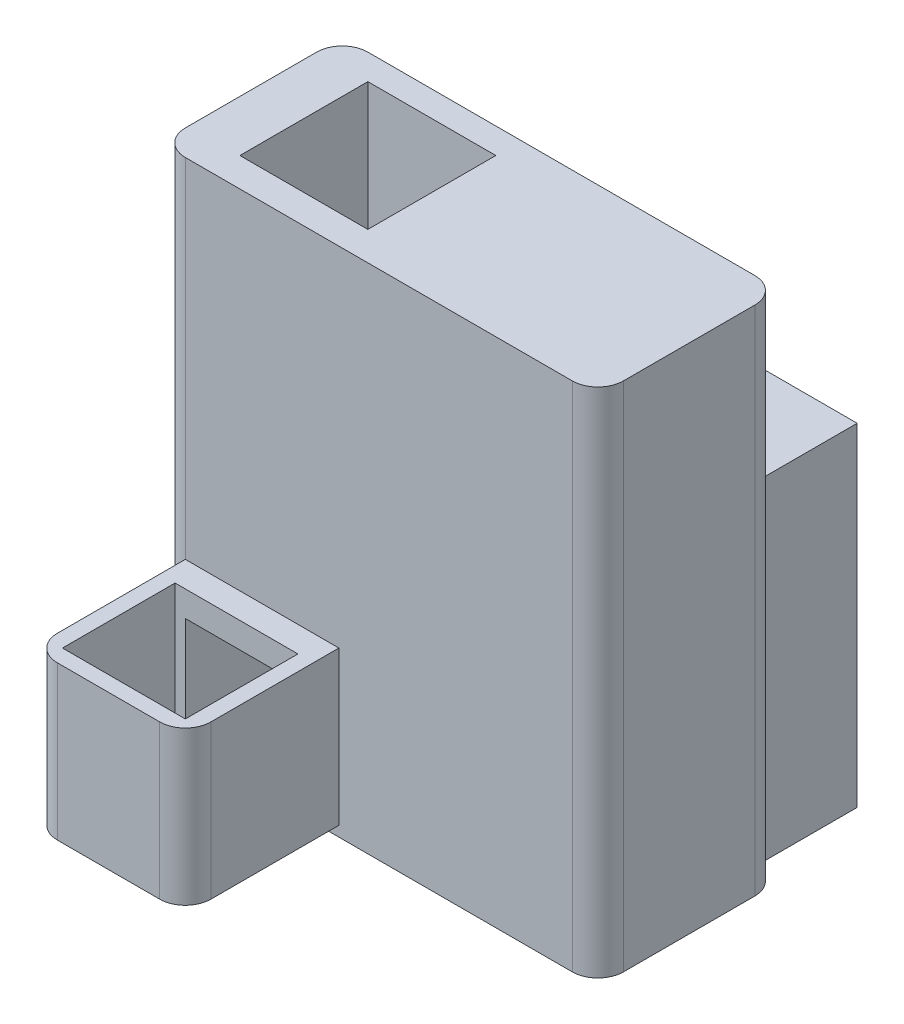
SolidWorks part; units mm, degrees
ref_plane "Alzado" through (0, 0, 0) normal (0, 0, 1) x (1, 0, 0)
ref_plane "Planta" through (0, 0, 0) normal (0, 1, 0) x (1, 0, 0)
ref_plane "Vista lateral" through (0, 0, 0) normal (1, 0, 0) x (0, 0, -1)
sketch "Croquis1" plane through (0, 0, 0) normal (0, 1, 0) x (1, 0, 0)
  line L1 (-42.8, 17.83) -> (42.8, 17.83)
  line L2 (-42.8, 17.83) -> (-42.8, -17.83)
  line L3 (-42.8, -17.83) -> (42.8, -17.83)
  line L4 (42.8, 17.83) -> (42.8, -17.83)
  line L5 (-42.8, 17.83) -> (42.8, -17.83) construction
  line L6 (-42.8, -17.83) -> (42.8, 17.83) construction
  point P0 (0, 0)
  dimension "D1" = 85.6
  dimension "D2" = 35.66
extrude "Saliente-Extruir1" add sketch "Croquis1" along normal blind 100
sketch "Croquis2" plane through (0, 100, 0) normal (0, 1, 0) x (1, 0, 0)
  line L0 (42.8, 17.83) -> (-42.8, 17.83) construction
  line L1 (-32.8, 12.83) -> (-7.8, 12.83)
  line L2 (-32.8, 12.83) -> (-32.8, -12.17)
  line L3 (-32.8, -12.17) -> (-7.8, -12.17)
  line L4 (-7.8, 12.83) -> (-7.8, -12.17)
  line L5 (-32.8, 12.83) -> (-7.8, -12.17) construction
  line L6 (-32.8, -12.17) -> (-7.8, 12.83) construction
  line L7 (-42.8, 17.83) -> (-42.8, -17.83) construction
  point P0 (-20.3, 0.33)
  dimension "D1" = 5
  dimension "D2" = 10
  dimension "D3" = 25
  dimension "D4" = 25
extrude "Cortar-Extruir1" cut sketch "Croquis2" against normal blind 92
sketch "Croquis3" plane through (0, 0, 17.83) normal (0, 0, 1) x (1, 0, 0)
  line L0 (-42.8, 100) -> (-42.8, 0) construction
  line L1 (-37.8, 32) -> (-7.8, 32)
  line L2 (-37.8, 32) -> (-37.8, 2)
  line L3 (-37.8, 2) -> (-7.8, 2)
  line L4 (-7.8, 32) -> (-7.8, 2)
  line L5 (-37.8, 32) -> (-7.8, 2) construction
  line L6 (-37.8, 2) -> (-7.8, 32) construction
  line L9 (-42.8, 0) -> (42.8, 0) construction
  point P0 (-22.8, 17)
  dimension "D1" = 5
  dimension "D2" = 2
  dimension "D3" = 30
  dimension "D4" = 30
extrude "Saliente-Extruir2" add sketch "Croquis3" along normal blind 30
sketch "Croquis4" plane through (0, 2, 0) normal (0, -1, 0) x (1, 0, 0)
  line L0 (-7.8, 47.83) -> (-7.8, 17.83) construction
  line L1 (-37.8, 47.83) -> (-37.8, 17.83) construction
  line L2 (-37.8, 47.83) -> (-7.8, 47.83) construction
  line L20 (-34.8, 22.83) -> (-10.8, 22.83)
  line L21 (-10.8, 22.83) -> (-10.8, 44.83)
  line L22 (-10.8, 44.83) -> (-34.8, 44.83)
  line L23 (-34.8, 44.83) -> (-34.8, 22.83)
  dimension "D1" = 3
  dimension "D2" = 3
  dimension "D3" = 3
extrude "Cortar-Extruir2" cut sketch "Croquis4" against normal up to surface (30 mm away) up to face at (-22.8, 32, 32.83)
sketch "Croquis6" plane through (0, 0, 17.83) normal (0, 0, 1) x (1, 0, 0)
  line L8 (-12.8, 7) -> (-12.8, 27)
  line L9 (-12.8, 27) -> (-32.8, 27)
  line L10 (-32.8, 27) -> (-32.8, 7)
  line L11 (-32.8, 7) -> (-12.8, 7)
  line L12 (-12.8, 7) -> (-12.8, 27)
  line L13 (-12.8, 27) -> (-32.8, 27)
  line L14 (-32.8, 27) -> (-32.8, 7)
  line L15 (-32.8, 7) -> (-12.8, 7)
  dimension "D1" = 5
fillet "Redondeo1" radius 5 6 edges at (42.8, 50, 17.83) (42.8, 50, -17.83) (-42.8, 50, -17.83) (-42.8, 50, 17.83) (-7.8, 17, 47.83) (-37.8, 17, 47.83)
sketch "Croquis8" plane through (0, 0, -17.83) normal (0, 0, -1) x (-1, 0, 0)
  line L0 (37.8, 0) -> (37.8, 100) construction
  line L1 (-37.8, 0) -> (37.8, 0)
  line L2 (-37.8, 0) -> (-37.8, 65)
  line L3 (-37.8, 65) -> (37.8, 65)
  line L4 (37.8, 0) -> (37.8, 65)
  dimension "D1" = 75.6
  dimension "D2" = 65
extrude "Saliente-Extruir3" add sketch "Croquis8" along normal blind 20
extrude "Cortar-Extruir3" cut sketch "Croquis6" against normal blind 10 and the other way blind 10
sketch "Croquis9" plane through (0, 2, 0) normal (0, -1, 0) x (1, 0, 0)
  line L0 (-10.8, 22.83) -> (-10.8, 44.83) construction
  line L1 (-34.8, 22.83) -> (-10.8, 22.83)
  line L2 (-34.8, 22.83) -> (-34.8, 44.83)
  line L3 (-34.8, 44.83) -> (-10.8, 44.83)
  line L4 (-10.8, 22.83) -> (-10.8, 44.83)
  line L5 (-10.8, 44.83) -> (-34.8, 44.83) construction
extrude "Saliente-Extruir4" add sketch "Croquis9" along normal blind 2 draft 60 separate body
sketch "Croquis10" plane through (0, 0, 0) normal (0, -1, 0) x (1, 0, 0)
  line L1 (-31.3359, 26.2941) -> (-14.2641, 26.2941)
  line L2 (-31.3359, 26.2941) -> (-31.3359, 41.3659)
  line L3 (-31.3359, 41.3659) -> (-14.2641, 41.3659)
  line L4 (-14.2641, 26.2941) -> (-14.2641, 41.3659)
extrude "Cortar-Extruir4" cut sketch "Croquis10" against normal up to surface (2 mm away) draft 25
sketch "Croquis12" plane through (0, 0, -37.83) normal (0, 0, -1) x (-1, 0, 0)
  line L8 (-32.8, 60) -> (-32.8, 5)
  line L9 (-32.8, 5) -> (32.8, 5)
  line L10 (32.8, 5) -> (32.8, 60)
  line L11 (32.8, 60) -> (-32.8, 60)
  line L12 (-32.8, 60) -> (-32.8, 5)
  line L13 (-32.8, 5) -> (32.8, 5)
  line L14 (32.8, 5) -> (32.8, 60)
  line L15 (32.8, 60) -> (-32.8, 60)
  dimension "D1" = 5
extrude "Cortar-Extruir6" cut sketch "Croquis12" against normal up to surface (20 mm away) up to face at (0, 82.5, -17.83)
sketch "Croquis17" plane through (0, 0, -17.83) normal (0, 0, -1) x (-1, 0, 0)
  line L0 (-32.8, 5) -> (32.8, 5) construction
  line L1 (-32.8, 60) -> (-2.8, 60)
  line L2 (-32.8, 60) -> (-32.8, 5)
  line L3 (-32.8, 5) -> (-2.8, 5)
  line L4 (-2.8, 60) -> (-2.8, 5)
  dimension "D1" = 30
extrude "Cortar-Extruir11" cut sketch "Croquis17" against normal blind 30
